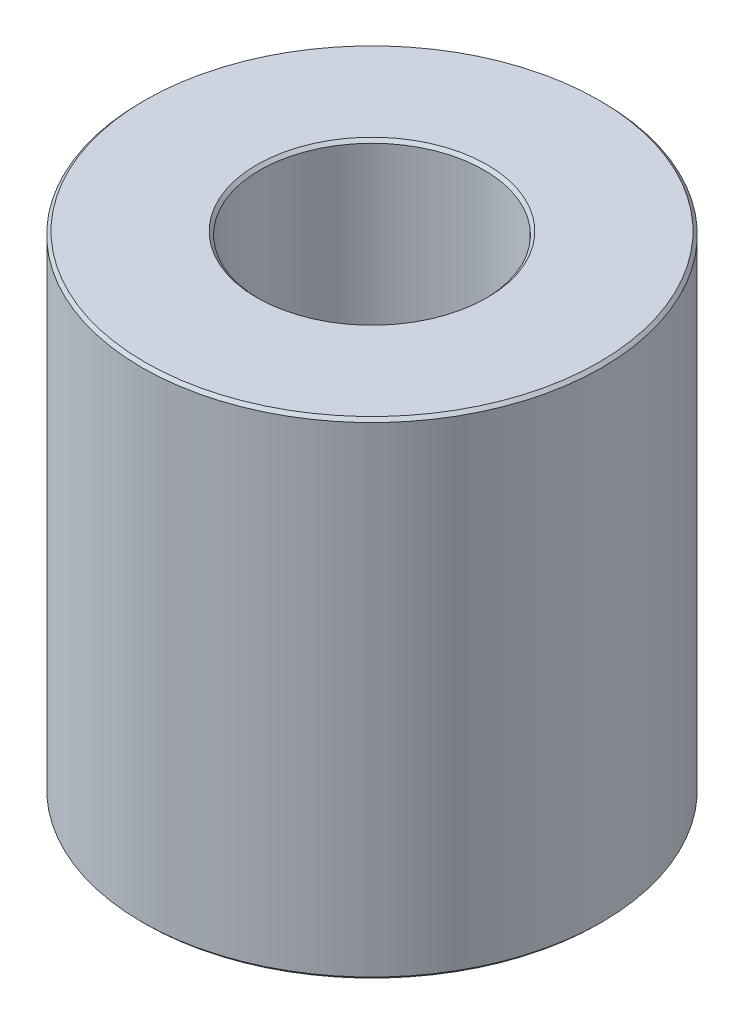
SolidWorks part; units mm, degrees
ref_plane "Front Plane" through (0, 0, 0) normal (0, 0, 1) x (1, 0, 0)
ref_plane "Top Plane" through (0, 0, 0) normal (0, 1, 0) x (1, 0, 0)
ref_plane "Right Plane" through (0, 0, 0) normal (1, 0, 0) x (0, 0, -1)
sketch "Sketch1" plane through (0, 0, 0) normal (0, 1, 0) x (1, 0, 0)
  circle A0 centre (0, 0) radius 37.5
  dimension "SLEEVE_OD" = 75
extrude "Boss-Extrude1" add sketch "Sketch1" along normal blind 79.2723
sketch "Sketch2" plane through (0, 0, 0) normal (0, 1, 0) x (1, 0, 0)
  circle A0 centre (0, 0) radius 18.2733
  dimension "BORE_D" = 36.5467
extrude "Cut-Extrude1" cut sketch "Sketch2" along normal through all
chamfer "Chamfer1" distance 0.5005 angle 45 4 edges at (0, 79.2723, 18.2733) (0, 0, 18.2733) (0, 0, 37.5) (0, 79.2723, 37.5)
